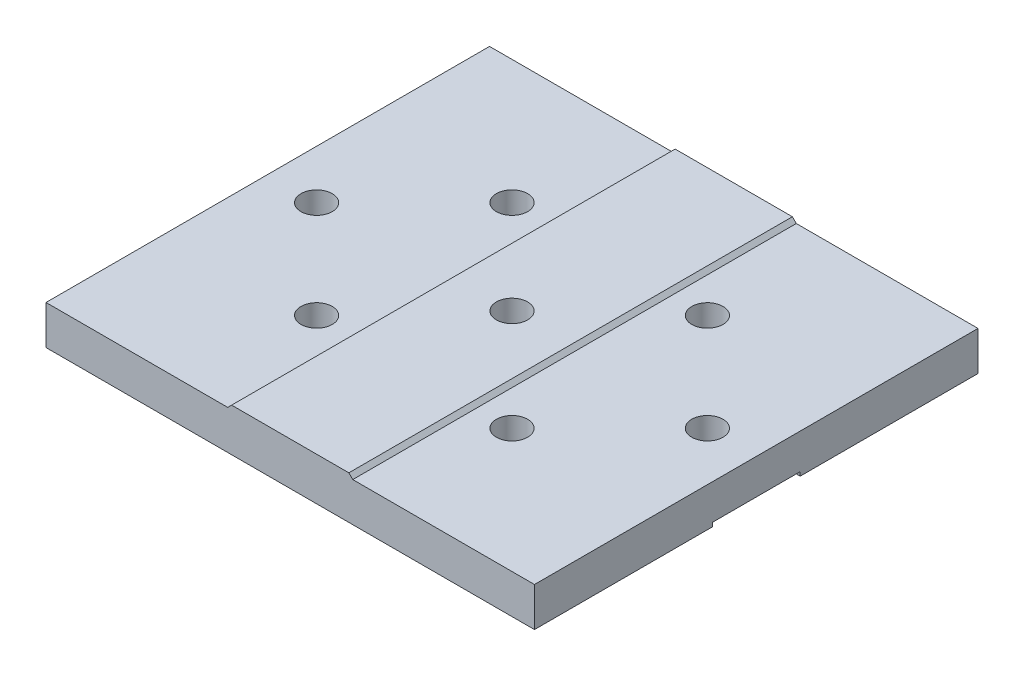
SolidWorks part; units mm, degrees
ref_plane "前视基准面" through (0, 0, 0) normal (0, 0, 1) x (1, 0, 0)
ref_plane "上视基准面" through (0, 0, 0) normal (0, 1, 0) x (1, 0, 0)
ref_plane "右视基准面" through (0, 0, 0) normal (1, 0, 0) x (0, 0, -1)
other "Configuration Table"
sketch "草图1" plane through (0, 0, 0) normal (0, 1, 0) x (1, 0, 0)
  line L1 (0, 0) -> (50, 0)
  line L2 (0, 0) -> (0, 45.4)
  line L3 (0, 45.4) -> (50, 45.4)
  line L4 (50, 0) -> (50, 45.4)
  circle A0 centre (15, 32.7) radius 1.6
  circle A1 centre (35, 32.7) radius 1.6
  circle A2 centre (35, 12.7) radius 1.6
  circle A3 centre (15, 12.7) radius 1.6
  dimension "D3" = 3.2
  dimension "D1" = 50
  dimension "D2" = 45.4
  dimension "D6" = 12.7
  dimension "D7" = 15
  dimension "D4" = 2
  dimension "D5" = 2
extrude "凸台-拉伸1" add sketch "草图1" along normal blind 4
sketch "草图2" plane through (0, 0, 0) normal (0, 0, 1) x (1, 0, 0)
  line L0 (0, 4) -> (50, 4) construction
  line L1 (19, 4) -> (31, 4)
  line L2 (19, 4) -> (19, 4.4)
  line L3 (19, 4.4) -> (31, 4.4)
  line L4 (31, 4) -> (31, 4.4)
  line L5 (0, 0) -> (50, 0) construction
  point P6 (25, 4.4)
  point P9 (25, 0)
  dimension "D1" = 0.4
  dimension "D2" = 12
  dimension "D3" = 0
extrude "凸台-拉伸2" add sketch "草图2" against normal up to surface (45.4 mm away) up to face at (25, 2, -45.4)
chamfer "倒角1" distance 0.4 angle 45 2 edges at (31, 4, -22.7) (19, 4, -22.7)
sketch "草图3" plane through (0, 0, 0) normal (0, -1, 0) x (-1, 0, 0)
  line L0 (0, 45.4) -> (0, 0) construction
  line L1 (0, 18.2) -> (-50, 18.2)
  line L2 (0, 18.2) -> (0, 27.2)
  line L3 (0, 27.2) -> (-50, 27.2)
  line L4 (-50, 18.2) -> (-50, 27.2)
  line L5 (-50, 0) -> (-50, 45.4) construction
  line L6 (0, 0) -> (-50, 0) construction
  point P8 (0, 22.7)
  dimension "D1" = 9
  dimension "D2" = 22.7
extrude "切除-拉伸1" cut sketch "草图3" against normal blind 0.4
sketch "草图4" plane through (0, 0.4, 0) normal (0, -1, 0) x (-1, 0, 0)
  line L0 (0, 18.2) -> (0, 27.2) construction
  circle A0 centre (-5, 22.7) radius 1.6
  circle A1 centre (-25, 22.7) radius 1.6
  circle A2 centre (-45, 22.7) radius 1.6
  point P4 (0, 22.7)
  dimension "D1" = 3.2
  dimension "D4" = 5
extrude "切除-拉伸2" cut sketch "草图4" against normal through all
equation "\"D7@草图1\"=\"D1@草图1\"/2-10"
equation "\"D6@草图1\"=\"D2@草图1\"/2-10"
equation "\"D2@草图3\"=\"D2@草图1\"/2"
equation "\"D4@草图4\"=\"D1@草图1\"/2-20"
